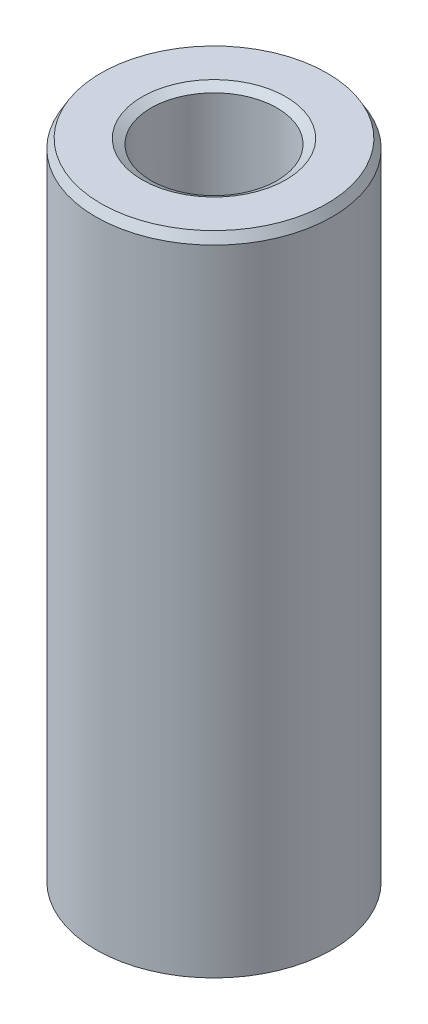
SolidWorks part; units mm, degrees
ref_plane "Front Plane" through (0, 0, 0) normal (0, 0, 1) x (1, 0, 0)
ref_plane "Top Plane" through (0, 0, 0) normal (0, 1, 0) x (1, 0, 0)
ref_plane "Right Plane" through (0, 0, 0) normal (1, 0, 0) x (0, 0, -1)
sketch "Sketch1" plane through (0, 0, 0) normal (0, 1, 0) x (1, 0, 0)
  circle A0 centre (0, 0) radius 45
  dimension "SLEEVE_OD" = 90
extrude "Boss-Extrude1" add sketch "Sketch1" along normal blind 246.9157
sketch "Sketch2" plane through (0, 0, 0) normal (0, 1, 0) x (1, 0, 0)
  circle A0 centre (0, 0) radius 23.9782
  dimension "BORE_D" = 47.9565
extrude "Cut-Extrude1" cut sketch "Sketch2" along normal through all
chamfer "Chamfer1" distance 3.4017 angle 30 4 edges at (0, 246.9157, 23.9782) (0, 0, 23.9782) (0, 0, 45) (0, 246.9157, 45) first distance on face at (0, 246.9157, 23.9782) first distance on face at (0, 0, 23.9782) first distance on face at (0, 246.9157, 45)
